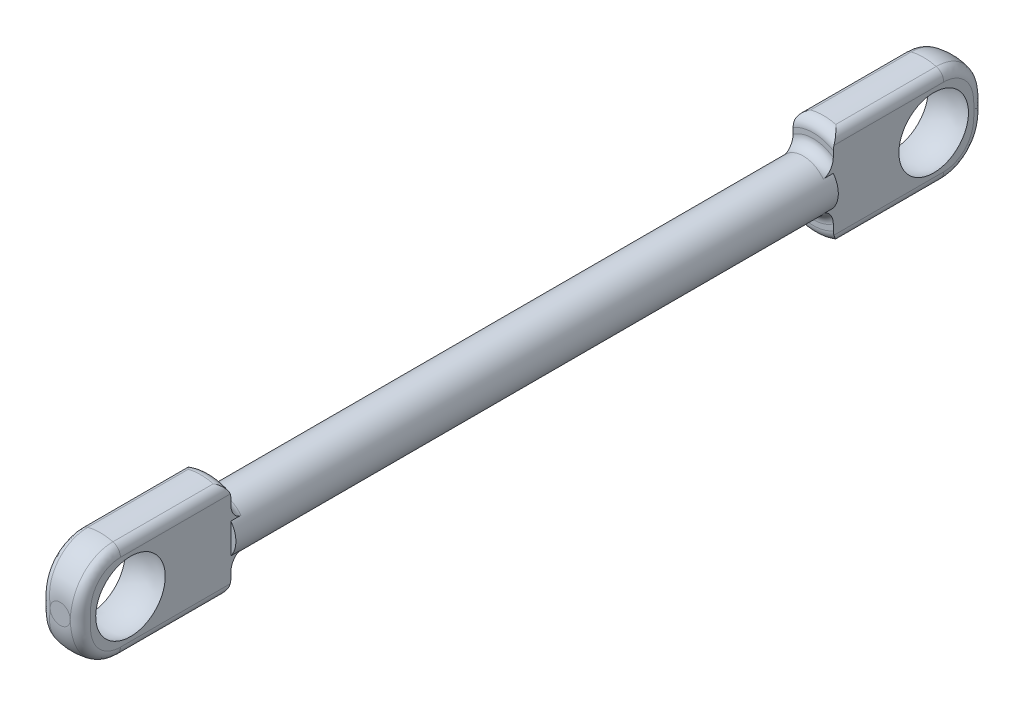
SolidWorks part; units mm, degrees
ref_plane "Plan de face" through (0, 0, 0) normal (0, 0, 1) x (1, 0, 0)
ref_plane "Plan de dessus" through (0, 0, 0) normal (0, 1, 0) x (1, 0, 0)
ref_plane "Plan de droite" through (0, 0, 0) normal (1, 0, 0) x (0, 0, -1)
sketch "Esquisse1" plane through (0, 0, 0) normal (0, 0, 1) x (1, 0, 0)
  circle A0 centre (0, 0) radius 5
  dimension "D1" = 10
extrude "Extrusion1" add sketch "Esquisse1" along normal blind 90
sketch "Esquisse2" plane through (0, 0, 90) normal (0, 0, 1) x (1, 0, 0)
  line L0 (-2, 4.5826) -> (-2, -4.5826)
  line L1 (-2, -4.5826) -> (-5, -4.5826)
  line L2 (-5, -4.5826) -> (-5, 4.5826)
  line L3 (-5, 4.5826) -> (-2, 4.5826)
  line L4 (2, 4.5826) -> (5, 4.5826)
  line L5 (5, 4.5826) -> (5, -4.5826)
  line L6 (5, -4.5826) -> (2, -4.5826)
  line L7 (2, -4.5826) -> (2, 4.5826)
  line L8 (2, 4.5826) -> (-2, -4.5826) construction
  circle A0 centre (0, 0) radius 5 construction
  dimension "D1" = 4
extrude "Extrusion2" cut sketch "Esquisse2" against normal blind 15
sketch "Esquisse3" plane through (0, 0, 0) normal (0, 0, -1) x (-1, 0, 0)
  line L0 (-2, 4.5826) -> (-2, -4.5826)
  line L1 (-2, -4.5826) -> (-5, -4.5826)
  line L2 (-5, -4.5826) -> (-5, 4.5826)
  line L3 (-5, 4.5826) -> (-2, 4.5826)
  line L4 (2, 4.5826) -> (5, 4.5826)
  line L5 (5, 4.5826) -> (5, -4.5826)
  line L6 (5, -4.5826) -> (2, -4.5826)
  line L7 (2, -4.5826) -> (2, 4.5826)
  line L8 (2, -4.5826) -> (-2, 4.5826) construction
  line L9 (0, 0) -> (0, -4.7679) construction
  circle A0 centre (0, 0) radius 5 construction
  dimension "D2" = 4
extrude "Extrusion3" cut sketch "Esquisse3" against normal blind 15
ref_plane "Plan1" through (0, 0, 0) normal (1, 0, 0) x (0, 0, -1)
sketch "Esquisse4" plane through (0, 0, 0) normal (1, 0, 0) x (0, 0, -1)
  line L0 (-89, 0) -> (-81, 0)
  line L1 (-90, 4.5826) -> (-90, -4.5826) construction
  line L2 (-90, 4.5826) -> (-75, -4.5826) construction
  line L3 (-85, 0) -> (-82.5, 0) construction
  arc A0 (-81, 0) -> (-89, 0) centre (-85, 0) ccw
  dimension "D1" = 8
  dimension "D2" = 5
revolve "Enlèvement de matière-Révolution1" cut sketch "Esquisse4" angle 360 about L0
ref_plane "Plan2" through (0, 0, 0) normal (1, 0, 0) x (0, 0, -1)
sketch "Esquisse5" plane through (0, 0, 0) normal (1, 0, 0) x (0, 0, -1)
  line L0 (-15, -4.5826) -> (0, 4.5826) construction
  line L1 (-9, 0) -> (-1, 0)
  line L2 (-5, 0) -> (-7.5, 0) construction
  line L3 (0, -4.5826) -> (0, 4.5826) construction
  arc A0 (-1, 0) -> (-9, 0) centre (-5, 0) ccw
  dimension "D1" = 8
  dimension "D2" = 5
revolve "Enlèvement de matière-Révolution2" cut sketch "Esquisse5" angle 360 about L1
ref_plane "Plan3" through (0, 0, 15) normal (0, 0, -1) x (-1, 0, 0)
sketch "Esquisse6" plane through (0, 0, 15) normal (0, 0, -1) x (-1, 0, 0)
  circle A0 centre (0, 0) radius 10
  circle A1 centre (0, 0) radius 2.5
  dimension "D1" = 5
  dimension "D2" = 20
extrude "Extrusion4" cut sketch "Esquisse6" against normal up to surface (60 mm away) up to face at (3.5, 0, 75)
fillet "Congé2" radius 4 2 edges at (0, 5, 0) (0, -5, 90)
fillet "Congé1" radius 1 20 edges at (-2, 1.6635, 0.3345) (2, -1.6635, 0.3345) (-2, -1.6635, 89.6655) (2, 1.6635, 89.6655) (2, 4.5826, 80.5) (-2, 4.5826, 80.5) (-2, 4.5826, 9.5) (2, 4.5826, 9.5) (2, -4.5826, 80.5) (-2, -4.5826, 80.5) (-2, -4.5826, 9.5) (2, -4.5826, 9.5) (0, -2.5, 15) (0, -5, 15) (0, 2.5, 15) (0, 5, 15) (0, -5, 75) (0, 5, 75) (0, 2.5, 75) (0, -2.5, 75)
